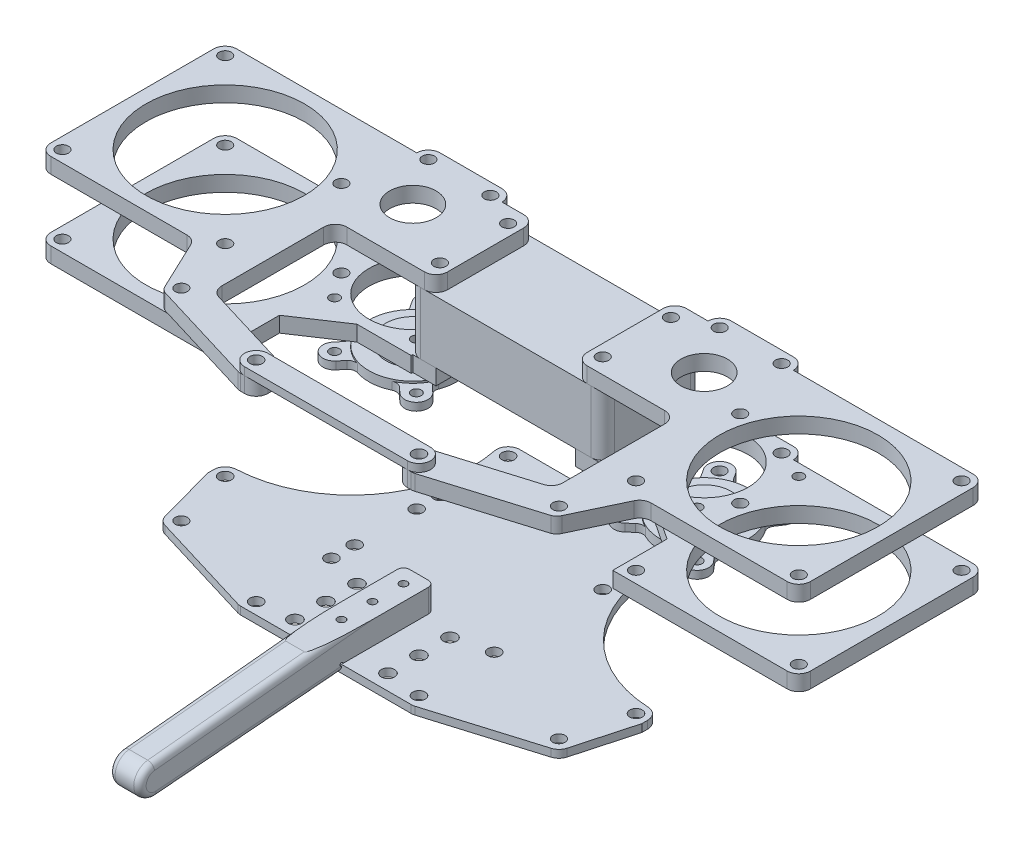
SolidWorks part; units mm, degrees
note: The reader was unsure of these and kept them because the rebuilt part matched: shared geometry of "Sketch14<2>".
material "Alum Plate"
ref_plane "Front Plane" through (0, 0, 0) normal (0, 0, 1) x (1, 0, 0)
ref_plane "Top Plane" through (0, 0, 0) normal (0, 1, 0) x (1, 0, 0)
ref_plane "Right Plane" through (0, 0, 0) normal (1, 0, 0) x (0, 0, -1)
sketch "Sketch1" plane through (0, 0, 0) normal (0, 1, 0) x (1, 0, 0)
  line L0 (0, 0) -> (117.475, 0) construction
  line L1 (-117.475, 0) -> (0, 0) construction
  line L3 (-9.525, 197.485) -> (-3.175, 197.485)
  line L4 (-9.525, 197.485) -> (-9.525, 70.485)
  line L5 (-9.525, 70.485) -> (-3.175, 70.485)
  line L6 (-3.175, 197.485) -> (-3.175, 70.485)
  line L7 (-9.525, 197.485) -> (-3.175, 70.485) construction
  line L8 (-9.525, 70.485) -> (-3.175, 197.485) construction
  line L14 (-155.575, -76.2) -> (155.575, -76.2)
  line L20 (-28.575, 38.1) -> (0, 38.1) construction
  line L21 (-6.35, 133.985) -> (0, 133.985)
  line L29 (0, 0) -> (0, -18.415) construction
  line L30 (-117.475, 0) -> (-59.6589, 19.05) construction
  line L43 (59.6589, 19.05) -> (117.475, 0) construction
  line L44 (-86.6074, 10.1707) -> (-86.2044, 10.3034)
  line L55 (-77.1578, 13.2842) -> (-76.7548, 13.417)
  line L69 (-155.575, -76.2) -> (-155.575, 38.1)
  line L70 (-155.575, 38.1) -> (155.575, 38.1)
  line L71 (155.575, -76.2) -> (155.575, 38.1)
  line L78 (0, 133.985) -> (0, -18.415)
  line L79 (0, -18.415) -> (0, -170.815) construction
  line L80 (-9.525, -234.315) -> (-3.175, -234.315) construction
  line L81 (-9.525, -234.315) -> (-9.525, -107.315) construction
  line L82 (-9.525, -107.315) -> (-3.175, -107.315) construction
  line L83 (-3.175, -234.315) -> (-3.175, -107.315) construction
  line L84 (-9.525, -234.315) -> (-3.175, -107.315) construction
  line L85 (-9.525, -107.315) -> (-3.175, -234.315) construction
  line L86 (0, -170.815) -> (-6.35, -170.815) construction
  line L87 (-38.1, -76.2) -> (-28.575, -76.2)
  line L88 (-38.1, -76.2) -> (-38.1, 38.1)
  line L89 (-38.1, 38.1) -> (-28.575, 38.1)
  line L90 (-28.575, -76.2) -> (-28.575, 38.1)
  line L91 (38.1, -76.2) -> (28.575, -76.2)
  line L92 (38.1, -76.2) -> (38.1, 38.1)
  line L93 (38.1, 38.1) -> (28.575, 38.1)
  line L94 (28.575, -76.2) -> (28.575, 38.1)
  line L95 (0, 38.1) -> (28.575, 38.1) construction
  circle A0 centre (-117.475, 0) radius 32.5
  circle A1 centre (-117.475, 0) radius 25
  circle A2 centre (117.475, 0) radius 32.5
  circle A3 centre (117.475, 0) radius 25
  circle A4 centre (-59.6589, 19.05) radius 18
  circle A5 centre (59.6589, 19.05) radius 18
  circle A8 centre (-81.6811, 11.7938) radius 4.7625
  point P8 (-6.35, 133.985)
  point P21 (117.475, 32.5)
  point P25 (59.6589, 37.05)
  point P29 (59.6589, 1.05)
  point P31 (0, -76.2)
  point P32 (-6.35, -170.815)
  point P62 (149.975, 0)
  dimension "D1" = 50
  dimension "D2" = 65
  dimension "D8" = 36
  dimension "D11" = 152.4
  dimension "D12" = 56.515
  dimension "D16" = 9.525
  dimension "D3" = 127
  dimension "D4" = 6.35
  dimension "D5" = 234.95
  dimension "D6" = 38.1
  dimension "D7" = 38.1
  dimension "D9" = 114.3
  dimension "D10" = 9.525
  dimension "D13" = 9.525
  dimension "D14" = 57.15
  dimension "D15" = 60.8736
  dimension "D18" = 19.05
sketch "Sketch2" plane through (0, 0, 0) normal (1, 0, 0) x (0, 0, -1)
  line L0 (0, 25.4) -> (0, 57.475) construction
  line L1 (-32.5, 60.975) -> (32.5, 60.975)
  line L2 (-32.5, 60.975) -> (-32.5, 53.975)
  line L3 (-32.5, 53.975) -> (32.5, 53.975)
  line L4 (32.5, 60.975) -> (32.5, 53.975)
  line L5 (-32.5, 60.975) -> (32.5, 53.975) construction
  line L6 (-32.5, 53.975) -> (32.5, 60.975) construction
  line L7 (-32.5, 92.075) -> (32.5, 92.075)
  line L8 (-32.5, 92.075) -> (-32.5, 85.075)
  line L9 (-32.5, 85.075) -> (32.5, 85.075)
  line L10 (32.5, 92.075) -> (32.5, 85.075)
  line L11 (-32.5, 92.075) -> (32.5, 85.075) construction
  line L12 (-32.5, 85.075) -> (32.5, 92.075) construction
  line L13 (-25.8191, 0) -> (33.9817, 0) construction
  line L14 (-18.415, 76.2) -> (-170.815, 76.2)
  line L15 (-76.2, 92.075) -> (38.1, 92.075)
  line L16 (-76.2, 92.075) -> (-76.2, 53.975)
  line L17 (-76.2, 53.975) -> (38.1, 53.975)
  line L18 (38.1, 92.075) -> (38.1, 53.975)
  line L19 (-5.8284, 26.8817) -> (0.4649, 73.66)
  line L20 (-18.415, 28.575) -> (-18.415, 76.2) construction
  line L21 (133.985, 0) -> (-18.415, 0) construction
  line L22 (-76.2, 85.725) -> (38.1, 85.725)
  line L23 (-76.2, 60.325) -> (38.1, 60.325)
  line L24 (-31.0016, 26.8817) -> (-37.2949, 73.66)
  line L25 (-18.415, 28.575) -> (-24.765, 64.8535) construction
  line L26 (-18.415, 76.2) -> (133.985, 76.2)
  line L32 (-76.2, 9.525) -> (38.1, 9.525)
  line L33 (-76.2, 9.525) -> (-76.2, 6.35)
  line L38 (-76.2, 6.35) -> (38.1, 6.35)
  line L39 (38.1, 9.525) -> (38.1, 6.35)
  line L40 (1.05, 41.2242) -> (37.05, 41.2242)
  line L41 (1.05, 41.2242) -> (1.05, 85.725)
  line L42 (1.05, 85.725) -> (37.05, 85.725)
  line L43 (37.05, 41.2242) -> (37.05, 85.725)
  line L44 (1.05, 41.2242) -> (37.05, 85.725) construction
  line L45 (1.05, 85.725) -> (37.05, 41.2242) construction
  line L46 (-38.1, 92.075) -> (-38.1, 53.975)
  line L47 (-38.1, 73.025) -> (0, 73.025) construction
  line L48 (0, 73.025) -> (38.1, 73.025) construction
  line L49 (-76.2, 9.525) -> (38.1, 6.35) construction
  line L50 (-76.2, 6.35) -> (38.1, 9.525) construction
  circle A0 centre (0, 25.4) radius 25.4
  circle A3 centre (-170.815, 76.2) radius 63.5
  circle A4 centre (-18.415, 76.2) radius 6.35
  circle A5 centre (-18.415, 28.575) radius 18
  circle A6 centre (133.985, 76.2) radius 63.5
  circle A7 centre (-18.415, 76.2) radius 19.05
  circle A8 centre (-18.415, 28.575) radius 12.7
  circle A9 centre (-24.765, 64.8535) radius 17.5006
  point P2 (0, 57.475)
  point P8 (0, 88.575)
  point P16 (-0.415, 28.575)
  point P28 (-36.415, 28.575)
  point P32 (19.05, 63.4746)
  point P34 (-234.315, 76.2)
  point P47 (0, 50.8)
  point P57 (-19.05, 7.9375)
  dimension "D1" = 50.8
  dimension "D8" = 38.1
  dimension "D2" = 25.4
  dimension "D11" = 12.7
  dimension "D12" = 36
  dimension "D14" = 35.0012
  dimension "D17" = 36.83
  dimension "D3" = 7
  dimension "D4" = 38.1
  dimension "D5" = 3.175
  dimension "D6" = 6.35
  dimension "D7" = 6.35
  dimension "D9" = 76.2
  dimension "D10" = 44.5008
  dimension "D13" = 47.625
  dimension "D15" = 3.175
  dimension "D16" = 25.4
  dimension "D18" = 44.45
  dimension "D19" = 6.35
sketch "Sketch5" plane through (0, 0, 0) normal (0, 1, 0) x (1, 0, 0)
  line L0 (-100.076, -18.415) -> (-28.575, -18.415) construction
  line L1 (-100.076, -4.415) -> (-68.58, -4.415)
  line L2 (-100.076, -4.415) -> (-100.076, -32.415)
  line L3 (-100.076, -32.415) -> (-68.58, -32.415)
  line L4 (-68.58, -4.415) -> (-68.58, -32.415)
  line L5 (-100.076, -4.415) -> (-68.58, -32.415) construction
  line L6 (-100.076, -32.415) -> (-68.58, -4.415) construction
  line L11 (-28.575, -76.2) -> (-28.575, 38.1) construction
  line L13 (-68.58, -0.415) -> (-28.575, -0.415)
  line L14 (-68.58, -0.415) -> (-68.58, -36.415)
  line L15 (-68.58, -36.415) -> (-28.575, -36.415)
  line L16 (-28.575, -0.415) -> (-28.575, -36.415)
  line L17 (-68.58, -0.415) -> (-28.575, -36.415) construction
  line L18 (-68.58, -36.415) -> (-28.575, -0.415) construction
  point P0 (-84.328, -18.415)
  point P10 (-48.5775, -18.415)
  dimension "D1" = 40.005
  dimension "D2" = 31.496
  dimension "D3" = 28
ref_plane "Plane1" through (0, 85.725, 0) normal (0, 1, 0) x (1, 0, 0)
ref_plane "Plane2" through (0, 60.325, 0) normal (0, -1, 0) x (-1, 0, 0)
ref_plane "Plane3" through (28.575, 0, 0) normal (1, 0, 0) x (0, 0, -1)
sketch "Sketch6" plane through (28.575, 0, 0) normal (1, 0, 0) x (0, 0, -1)
  line L0 (-18.415, 92.075) -> (-18.415, 76.2) construction
  line L2 (-76.2, 60.325) -> (-66.04, 92.075)
  line L3 (-76.2, 92.075) -> (38.1, 92.075) construction
  line L4 (-66.04, 92.075) -> (-62.865, 92.075)
  line L5 (-62.865, 92.075) -> (-62.865, 85.725)
  line L6 (-76.2, 85.725) -> (38.1, 85.725) construction
  line L7 (-62.865, 85.725) -> (-34.29, 85.725)
  line L8 (-2.54, 60.325) -> (-2.54, 53.975)
  line L10 (-32.5, 53.975) -> (32.5, 53.975) construction
  line L11 (-76.2, 53.975) -> (-76.2, 60.325)
  line L12 (-76.2, 53.975) -> (-2.54, 53.975)
  line L13 (-34.29, 85.725) -> (-34.29, 92.075)
  line L14 (-34.29, 92.075) -> (-2.54, 92.075)
  line L15 (-2.54, 85.725) -> (-2.54, 92.075)
  line L16 (-34.29, 85.725) -> (-2.54, 92.075) construction
  line L17 (-34.29, 92.075) -> (-2.54, 85.725) construction
  line L19 (-76.2, 60.325) -> (38.1, 60.325) construction
  line L20 (-2.54, 60.325) -> (38.1, 60.325)
  line L21 (-2.54, 60.325) -> (-2.54, 85.725) construction
  line L22 (-2.54, 85.725) -> (38.1, 85.725)
  line L23 (38.1, 60.325) -> (38.1, 85.725)
  line L24 (-2.54, 60.325) -> (38.1, 85.725) construction
  line L25 (-2.54, 85.725) -> (38.1, 60.325) construction
  line L26 (-2.54, 85.725) -> (-2.54, 60.325) construction
  point P10 (-18.415, 88.9)
  point P28 (17.78, 73.025)
  dimension "D2" = 44.45
  dimension "D3" = 3.175
  dimension "D4" = 31.75
extrude "Boss-Extrude1" add sketch "Sketch6" along normal up to vertex (9.525 mm away) up to point (38.1, 0, -38.1)
sketch "Sketch7" plane through (0, 85.725, 0) normal (0, 1, 0) x (1, 0, 0)
  line L0 (28.575, -62.865) -> (80.3409, -62.865)
  line L2 (155.575, -76.2) -> (155.575, 38.1) construction
  line L3 (155.575, -38.1) -> (155.575, 38.1)
  line L4 (155.575, 38.1) -> (28.575, 38.1)
  line L5 (28.575, 38.1) -> (28.575, -2.54)
  line L6 (155.575, -38.1) -> (117.475, -38.1)
  line L8 (117.475, 38.1) -> (117.475, 0) construction
  line L9 (117.475, 0) -> (117.475, -38.1) construction
  line L10 (28.575, -34.29) -> (38.1, -34.29)
  line L11 (38.1, -34.29) -> (38.1, -2.54)
  line L12 (38.1, -2.54) -> (28.575, -2.54)
  line L13 (28.575, -76.2) -> (28.575, 38.1) construction
  line L14 (28.575, -34.29) -> (28.575, -62.865)
  line L15 (117.475, -38.1) -> (92.075, -38.1)
  line L16 (92.075, -38.1) -> (80.3409, -62.865)
  circle A0 centre (117.475, 0) radius 32.5 construction
  circle A1 centre (117.475, 0) radius 32.5
  circle A3 centre (59.6589, 19.05) radius 9.525
  dimension "D1" = 51.7659
  dimension "D2" = 19.05
  dimension "D3" = 25.4
extrude "Boss-Extrude2" add sketch "Sketch7" along normal up to surface (6.35 mm away) separate body up to face at (33.3375, 92.075, 64.4525)
sketch "Sketch8" plane through (0, 60.325, 0) normal (0, -1, 0) x (-1, 0, 0)
  line L1 (-79.375, -38.1) -> (-155.575, -38.1)
  line L2 (-79.375, -38.1) -> (-79.375, 38.1) construction
  line L3 (-79.375, 38.1) -> (-155.575, 38.1)
  line L4 (-155.575, -38.1) -> (-155.575, 38.1)
  line L5 (-79.375, -38.1) -> (-155.575, 38.1) construction
  line L6 (-79.375, 38.1) -> (-155.575, -38.1) construction
  line L7 (155.575, 38.1) -> (-155.575, 38.1) construction
  line L8 (-28.575, 38.1) -> (-79.375, 38.1)
  line L12 (-79.375, -38.1) -> (-79.375, -3.175)
  line L13 (-79.375, -3.175) -> (-38.1, -3.175)
  line L14 (-38.1, -76.2) -> (-38.1, 38.1) construction
  line L15 (-38.1, -3.175) -> (-38.1, -2.54)
  line L16 (-38.1, -2.54) -> (-28.575, -2.54)
  line L17 (-28.575, -2.54) -> (-28.575, 38.1)
  circle A0 centre (-117.475, 0) radius 32.5 construction
  circle A1 centre (-117.475, 0) radius 32.5
  circle A3 centre (-59.6589, 19.05) radius 18
  circle A4 centre (-59.6589, 19.05) radius 18 construction
  dimension "D1" = 22.225
extrude "Boss-Extrude3" add sketch "Sketch8" along normal up to vertex (6.35 mm away) separate body up to point (0, 53.975, -38.1)
sketch "Sketch14" plane through (0, 60.325, 0) normal (0, 1, 0) x (1, 0, 0)
  line L0 (59.6589, 38.1) -> (59.6589, 19.05) construction
  line L1 (72.3589, 42.8625) -> (46.9589, 42.8625)
  line L2 (28.575, 38.1) -> (155.575, 38.1) construction
  line L3 (67.5964, 38.1) -> (51.7214, 38.1)
  arc A0 (67.5964, 38.1) -> (72.3589, 42.8625) centre (72.3589, 38.1) ccw
  arc A1 (46.9589, 42.8625) -> (51.7214, 38.1) centre (46.9589, 38.1) ccw
  dimension "D1" = 9.525
  dimension "D2" = 25.4
extrude "Boss-Extrude4" add sketch "Sketch14" against normal up to surface (6.35 mm away) up to face at (117.475, 53.975, -32.5)
extrude "Boss-Extrude5" add sketch "Sketch14<2>" against normal up to surface (6.35 mm away) from surface at 31.75 up to face at (67.4066, 85.725, 19.939) starting at face at (59.6589, 92.075, -28.575)
sketch "Sketch14<2>" plane through (0, 60.325, 0) normal (0, 1, 0) x (1, 0, 0) same geometry as "Sketch14"
sketch "Sketch15" plane through (0, 53.975, 0) normal (0, -1, 0) x (1, 0, 0)
  line L0 (-81.6811, -11.7938) -> (81.6811, -11.7938) construction
  line L1 (59.6589, -19.05) -> (117.475, 0) construction
  line L2 (79.375, 38.1) -> (79.375, 3.175) construction
  line L3 (155.575, 38.1) -> (79.375, 38.1) construction
  line L4 (155.575, 76.2) -> (155.575, -38.1) construction
  line L5 (-155.575, -38.1) -> (155.575, -38.1) construction
  line L6 (150.8125, 38.1) -> (155.575, 38.1)
  line L7 (155.575, 38.1) -> (155.575, 33.3375)
  line L8 (150.8125, -38.1) -> (155.575, -38.1)
  line L9 (155.575, -38.1) -> (155.575, -33.3375)
  line L10 (33.3375, -38.1) -> (33.3375, -31.75) construction
  line L11 (33.3375, -31.75) -> (33.3375, -3.81) construction
  line L12 (33.3375, -3.81) -> (33.3375, 2.54) construction
  line L13 (38.1, 2.54) -> (28.575, 2.54) construction
  line L14 (33.3375, 2.54) -> (33.3375, -3.81) construction
  line L15 (33.3375, 34.29) -> (33.3375, 40.64) construction
  line L16 (33.3375, 40.64) -> (33.3375, 56.515) construction
  line L18 (38.1, 34.29) -> (28.575, 34.29) construction
  line L19 (38.1, 2.54) -> (28.575, 2.54) construction
  line L20 (33.3375, 2.54) -> (33.3375, -3.81) construction
  line L21 (77.3274, 62.865) -> (77.3274, 58.1025) construction
  line L22 (28.575, 62.865) -> (80.3409, 62.865) construction
  line L23 (77.3274, 58.1025) -> (81.6312, 60.1417) construction
  line L24 (80.3409, 62.865) -> (92.075, 38.1) construction
  line L25 (33.3375, 56.515) -> (33.3375, 62.865) construction
  line L26 (80.3409, 62.865) -> (28.575, 62.865) construction
  circle A0 centre (46.9589, -38.1) radius 2.4892
  circle A1 centre (72.3589, -38.1) radius 2.4892
  circle A3 centre (81.6811, -11.7938) radius 2.4892
  circle A4 centre (150.8125, -33.3375) radius 2.4892
  circle A5 centre (150.8125, 33.3375) radius 2.4892
  circle A6 centre (84.1375, 33.3375) radius 2.4892
  circle A7 centre (84.1375, 33.3375) radius 4.7625 construction
  arc A8 (155.575, 33.3375) -> (150.8125, 38.1) centre (150.8125, 33.3375) ccw
  arc A9 (150.8125, -38.1) -> (155.575, -33.3375) centre (150.8125, -33.3375) ccw
  arc A10 (155.575, -33.3375) -> (150.8125, -38.1) centre (150.8125, -33.3375) ccw construction
  arc A11 (150.8125, 38.1) -> (155.575, 33.3375) centre (150.8125, 33.3375) ccw construction
  circle A12 centre (33.3375, -31.75) radius 2.4892
  circle A14 centre (33.3375, -3.81) radius 2.4892
  circle A15 centre (33.3375, 40.64) radius 2.4892
  circle A16 centre (77.3274, 58.1025) radius 2.4892
  circle A17 centre (33.3375, 56.515) radius 2.4892
  dimension "D1" = 4.9784
  dimension "D2" = 9.525
  dimension "D3" = 6.35
  dimension "D4" = 6.35
  dimension "D5" = 4.7625
extrude "Cut-Extrude9" cut sketch "Sketch15" against normal through all
sketch "Sketch16" plane through (28.575, 0, 0) normal (-1, 0, 0) x (0, 0, 1)
  circle A0 centre (18.415, 76.2) radius 6.35 construction
  circle A1 centre (18.415, 76.2) radius 6.35
extrude "Cut-Extrude10" cut sketch "Sketch16" against normal up to next (9.525 mm away)
sketch "Sketch19" plane through (0, 53.975, 0) normal (0, -1, 0) x (1, 0, 0)
  line L0 (33.3375, 76.2) -> (33.3375, 71.4375) construction
  line L1 (38.1, 76.2) -> (28.575, 76.2) construction
  line L2 (33.3375, 71.4375) -> (38.1, 71.4375) construction
  line L3 (38.1, 76.2) -> (38.1, 2.54) construction
  circle A0 centre (33.3375, -3.81) radius 2.0193
  circle A1 centre (33.3375, -31.75) radius 2.0193
  circle A2 centre (33.3375, 40.64) radius 2.0193
  circle A3 centre (33.3375, 71.4375) radius 2.0193
  circle A4 centre (33.3375, 40.64) radius 2.4892 construction
  circle A5 centre (33.3375, 56.515) radius 2.0193
  dimension "D1" = 4.0386
extrude "Cut-Extrude11" cut sketch "Sketch19" against normal through all
sketch "Sketch22" plane through (0, 53.975, 0) normal (0, -1, 0) x (1, 0, 0)
  line L0 (150.8125, -33.3375) -> (84.1375, -33.3375) construction
  line L1 (84.1375, -33.3375) -> (84.1375, 33.3375) construction
  circle A0 centre (84.1375, -33.3375) radius 2.0193
  circle A1 centre (33.3375, -31.75) radius 2.0193 construction
extrude "Cut-Extrude12" cut sketch "Sketch22" against normal up to next (6.35 mm away)
chamfer "Chamfer1" distance 12.7 distance2 19.05 1 edges at (79.375, 57.15, 3.175)
mirror "Mirror2" about plane through (0, 0, 0) normal (1, 0, 0) of bodies 139 122 141 106 108 111
sketch "Sketch17" plane through (38.1, 0, 0) normal (1, 0, 0) x (0, 0, -1)
  circle A0 centre (-18.415, 76.2) radius 6.35 construction
  circle A1 centre (-18.415, 76.2) radius 6.35
extrude "Boss-Extrude6" add sketch "Sketch17" against normal up to surface (76.2 mm away) separate body up to face at (-38.1, 76.2, 24.765)
sketch "Sketch24" plane through (0, 53.975, 0) normal (0, -1, 0) x (1, 0, 0)
  line L1 (-38.1, 76.2) -> (38.1, 76.2)
  line L2 (-38.1, 76.2) -> (-38.1, -38.1)
  line L3 (-38.1, -38.1) -> (38.1, -38.1)
  line L4 (38.1, 76.2) -> (38.1, -38.1)
  line L5 (-38.1, 76.2) -> (38.1, -38.1) construction
  line L6 (-38.1, -38.1) -> (38.1, 76.2) construction
  circle A0 centre (-33.3375, 71.4375) radius 2.5527
  circle A1 centre (33.3375, 71.4375) radius 2.5527
  circle A2 centre (33.3375, 40.64) radius 2.5527
  circle A3 centre (-33.3375, 40.64) radius 2.5527
  circle A4 centre (-33.3375, -3.81) radius 2.5527
  circle A5 centre (33.3375, -3.81) radius 2.5527
  circle A6 centre (33.3375, -31.75) radius 2.5527
  circle A7 centre (-33.3375, -31.75) radius 2.5527
  circle A8 centre (33.3375, 56.515) radius 2.5527
  circle A9 centre (-33.3375, 56.515) radius 2.5527
  point P4 (0, 19.05)
  dimension "D1" = 5.1054
extrude "Boss-Extrude8" add sketch "Sketch24" along normal blind 3.175 separate body
sketch "Sketch25" plane through (0, 53.975, 0) normal (0, 1, 0) x (1, 0, 0)
  line L1 (-19.05, -43.815) -> (6.35, -43.815)
  line L2 (-19.05, -43.815) -> (-19.05, 6.985)
  line L3 (-19.05, 6.985) -> (6.35, 6.985)
  line L4 (6.35, -43.815) -> (6.35, 6.985)
  line L5 (-19.05, -43.815) -> (6.35, 6.985) construction
  line L6 (-19.05, 6.985) -> (6.35, -43.815) construction
  line L7 (-28.575, -76.2) -> (-28.575, -2.54) construction
  point P4 (-6.35, -18.415)
  dimension "D1" = 25.4
  dimension "D2" = 50.8
  dimension "D3" = 9.525
extrude "Cut-Extrude13" cut sketch "Sketch25" against normal through all
sketch "Sketch34" plane through (0, 53.975, 0) normal (0, -1, 0) x (1, 0, 0)
  line L0 (60.325, 3.175) -> (38.1, 3.175) construction
  line L1 (-60.325, 3.175) -> (-38.1, 3.175) construction
  line L2 (-38.1, 76.2) -> (-38.1, -38.1) construction
  line L3 (38.1, -38.1) -> (38.1, 76.2) construction
  circle A0 centre (74.26, -1.5875) radius 2.0193
  circle A1 centre (74.26, -1.5875) radius 4.7625 construction
  circle A3 centre (33.3375, -3.81) radius 2.0193 construction
  circle A4 centre (59.6589, -19.05) radius 18 construction
  circle A6 centre (-74.26, -1.5875) radius 4.7625 construction
  circle A7 centre (-74.26, -1.5875) radius 2.0193
  circle A8 centre (-59.6589, -19.05) radius 18 construction
  circle A9 centre (42.8625, -3.6873) radius 2.0193
  circle A10 centre (42.8625, -3.6873) radius 4.7625 construction
  circle A11 centre (-42.8625, -3.6873) radius 2.0193
  circle A12 centre (-42.8625, -3.6873) radius 4.7625 construction
  dimension "D1" = 9.525
extrude "Cut-Extrude20" cut sketch "Sketch34" against normal up to next (6.35 mm away)
ref_plane "Plane4" through (0, 9.525, 0) normal (0, -1, 0) x (-1, 0, 0)
sketch "Sketch21" plane through (0, 9.525, 0) normal (0, -1, 0) x (-1, 0, 0)
  line L0 (-84.1375, -33.3375) -> (-84.1375, 33.3375) construction
  line L1 (-84.1375, 33.3375) -> (-33.3375, 31.75) construction
  line L2 (-33.3375, 31.75) -> (33.3375, 31.75) construction
  line L3 (33.3375, 31.75) -> (84.1375, 33.3375) construction
  line L4 (84.1375, 33.3375) -> (84.1375, -33.3375) construction
  line L5 (84.1375, -33.3375) -> (33.3375, -71.4375) construction
  line L6 (33.3375, -71.4375) -> (-33.3375, -71.4375) construction
  line L7 (-33.3375, -71.4375) -> (-84.1375, -33.3375) construction
  line L8 (-88.9, -35.7188) -> (-88.9, 38.2512)
  line L9 (-88.9, 38.2512) -> (-33.2631, 36.5125)
  line L10 (-33.2631, 36.5125) -> (33.2631, 36.5125)
  line L11 (33.2631, 36.5125) -> (88.9, 38.2512)
  line L12 (88.9, 38.2512) -> (88.9, -35.7188)
  line L14 (34.925, -76.2) -> (-34.925, -76.2)
  line L16 (-84.1375, -33.3375) -> (-77.3274, -58.1025) construction
  line L17 (-77.3274, -58.1025) -> (-33.3375, -71.4375) construction
  line L18 (33.3375, -71.4375) -> (77.3274, -58.1025) construction
  line L19 (77.3274, -58.1025) -> (84.1375, -33.3375) construction
  line L20 (-88.9, -35.7188) -> (-81.6, -62.2655)
  line L21 (88.9, -35.7188) -> (34.925, -76.2) construction
  line L22 (-34.925, -76.2) -> (-88.9, -35.7188) construction
  line L23 (-81.6, -62.2655) -> (-35.6323, -76.2)
  line L24 (35.6323, -76.2) -> (81.6, -62.2655)
  line L25 (81.6, -62.2655) -> (88.9, -35.7188)
  line L26 (-89.174, -34.7225) -> (-81.6, -62.2655) construction
  line L27 (81.6, -62.2655) -> (89.174, -34.7225) construction
  line L28 (-34.925, -76.2) -> (-35.6323, -76.2)
  line L31 (-38.1, -76.2) -> (38.1, -76.2) construction
  line L32 (-81.6, -62.2655) -> (-34.8528, -76.4363) construction
  line L33 (34.925, -76.2) -> (35.6323, -76.2)
  line L34 (34.8528, -76.4363) -> (81.6, -62.2655) construction
  circle A0 centre (-84.1375, 33.3375) radius 2.5527
  circle A1 centre (-84.1375, -33.3375) radius 2.5527
  circle A2 centre (-33.3375, 31.75) radius 2.5527
  circle A3 centre (-33.3375, 3.81) radius 2.5527
  circle A4 centre (-33.3375, -40.64) radius 2.5527
  circle A5 centre (-33.3375, -71.4375) radius 2.5527
  circle A6 centre (33.3375, -71.4375) radius 2.5527
  circle A7 centre (33.3375, -40.64) radius 2.5527
  circle A8 centre (33.3375, 3.81) radius 2.5527
  circle A9 centre (33.3375, 31.75) radius 2.5527
  circle A10 centre (84.1375, 33.3375) radius 2.5527
  circle A11 centre (84.1375, -33.3375) radius 2.5527
  circle A12 centre (-77.3274, -58.1025) radius 2.4892 construction
  circle A13 centre (77.3274, -58.1025) radius 2.4892 construction
  circle A15 centre (-77.3274, -58.1025) radius 2.4892
  circle A17 centre (-74.26, 1.5875) radius 2.5527
  circle A18 centre (74.26, 1.5875) radius 2.5527
  circle A19 centre (-42.8625, 3.6873) radius 2.5527
  circle A20 centre (42.8625, 3.6873) radius 2.5527
  circle A21 centre (77.3274, -58.1025) radius 2.4892
  dimension "D1" = 5.1054
  dimension "D2" = 4.7625
extrude "Boss-Extrude7" add sketch "Sketch21" along normal up to vertex (3.175 mm away) separate body up to point (0, 6.35, -38.1)
sketch "Sketch26" plane through (-38.1, 0, 0) normal (-1, 0, 0) x (0, 0, 1)
  line L0 (76.2, 9.525) -> (-38.1, 9.525) construction
  line L1 (-10.16, 9.525) -> (46.99, 9.525)
  line L2 (-10.16, 9.525) -> (-10.16, 50.8)
  line L3 (-10.16, 50.8) -> (46.99, 50.8)
  line L4 (46.99, 9.525) -> (46.99, 50.8)
  line L5 (-10.16, 9.525) -> (46.99, 50.8) construction
  line L6 (-10.16, 50.8) -> (46.99, 9.525) construction
  line L7 (76.2, 50.8) -> (-38.1, 50.8) construction
  line L8 (18.415, 28.575) -> (18.415, 30.1625) construction
  circle A0 centre (18.415, 28.575) radius 18 construction
  circle A1 centre (18.415, 28.575) radius 18
  point P7 (18.415, 30.1625)
  dimension "D1" = 57.15
extrude "Boss-Extrude9" add sketch "Sketch26" against normal up to surface (9.525 mm away) separate body up to face at (-28.575, 76.2, 24.765)
sketch "Sketch27" plane through (0, 9.525, 0) normal (0, -1, 0) x (1, 0, 0)
  circle A0 centre (-33.3375, -3.81) radius 2.5527 construction
  circle A1 centre (-33.3375, 40.64) radius 2.5527 construction
  circle A2 centre (-33.3375, -3.81) radius 2.5527
  circle A3 centre (-33.3375, 40.64) radius 2.5527
extrude "Cut-Extrude14" cut sketch "Sketch27" against normal through all
sketch "Sketch28" plane through (-38.1, 0, 0) normal (-1, 0, 0) x (0, 0, 1)
  line L0 (-6.3627, 6.35) -> (-1.2573, 6.35) construction
  line L1 (-10.16, 9.525) -> (0.9525, 9.525)
  line L2 (-10.16, 9.525) -> (-10.16, 14.2875)
  line L3 (-10.16, 14.2875) -> (0.9525, 14.2875)
  line L4 (0.9525, 9.525) -> (0.9525, 14.2875)
  line L5 (-10.16, 9.525) -> (0.9525, 14.2875) construction
  line L6 (-10.16, 14.2875) -> (0.9525, 9.525) construction
  line L7 (46.99, 9.525) -> (35.8775, 9.525)
  line L8 (46.99, 9.525) -> (46.99, 14.2875)
  line L9 (46.99, 14.2875) -> (35.8775, 14.2875)
  line L10 (35.8775, 9.525) -> (35.8775, 14.2875)
  line L11 (46.99, 9.525) -> (35.8775, 14.2875) construction
  line L12 (46.99, 14.2875) -> (35.8775, 9.525) construction
  line L13 (-6.3627, 6.35) -> (-1.2573, 6.35) construction
  point P4 (-4.6038, 11.9062)
  point P10 (41.4337, 11.9062)
  point P14 (-3.81, 6.35)
  dimension "D1" = 4.7625
  dimension "D2" = 4.7625
extrude "Cut-Extrude15" cut sketch "Sketch28" against normal through all
sketch "Sketch30" plane through (0, 6.35, 0) normal (0, -1, 0) x (1, 0, 0)
  line L0 (-33.3375, -3.81) -> (-33.3375, 5.715) construction
  line L1 (-33.3375, 5.715) -> (-33.3375, 31.115) construction
  line L2 (-33.3375, 31.115) -> (-33.3375, 40.64) construction
  circle A0 centre (-33.3375, 31.115) radius 2.5527
  circle A1 centre (-33.3375, 5.715) radius 2.5527
  circle A2 centre (-33.3375, -3.81) radius 2.5527 construction
  dimension "D1" = 9.525
extrude "Cut-Extrude16" cut sketch "Sketch30" against normal through all
sketch "Sketch31" plane through (0, 9.525, 0) normal (0, -1, 0) x (1, 0, 0)
  circle A0 centre (-33.3375, 5.715) radius 2.0193
  circle A1 centre (-33.3375, 31.115) radius 2.0193
  circle A2 centre (-33.3375, -3.81) radius 2.0193 construction
extrude "Cut-Extrude17" cut sketch "Sketch31" against normal up to next
sketch "Sketch32" plane through (-38.1, 0, 0) normal (-1, 0, 0) x (0, 0, 1)
  line L0 (46.99, 14.2875) -> (46.99, 50.8) construction
  line L1 (-10.16, 28.702) -> (46.99, 28.702)
  line L2 (-10.16, 28.702) -> (-10.16, 28.448)
  line L3 (-10.16, 28.448) -> (46.99, 28.448)
  line L4 (46.99, 28.702) -> (46.99, 28.448)
  line L5 (-10.16, 28.702) -> (46.99, 28.448) construction
  line L6 (-10.16, 28.448) -> (46.99, 28.702) construction
  point P0 (18.415, 28.575)
  dimension "D1" = 0.254
extrude "Cut-Extrude18" cut sketch "Sketch32" against normal through all
sketch "Sketch33" plane through (0, 6.35, 0) normal (0, -1, 0) x (1, 0, 0)
  line L0 (88.9, -38.2512) -> (88.9, 35.7188) construction
  line L1 (88.9, -25.2008) -> (88.9, 25.2008)
  line L2 (-88.9, 35.7188) -> (-88.9, -38.2512) construction
  line L3 (-88.9, -25.2008) -> (-88.9, 25.2008)
  arc A0 (88.9, -25.2008) -> (88.9, 25.2008) centre (117.475, 0) cw
  arc A1 (-88.9, 25.2008) -> (-88.9, -25.2008) centre (-117.475, 0) cw
  dimension "D1" = 38.1
extrude "Cut-Extrude19" cut sketch "Sketch33" against normal up to surface (3.175 mm away) up to face at (-33.3375, 9.525, 28.5623)
fillet "Fillet1" radius 4.7625 10 edges at (88.9, 7.9375, -38.2512) (88.9, 7.9375, 25.2008) (88.9, 7.9375, -25.2008) (-88.9, 7.9375, -25.2008) (-88.9, 7.9375, 25.2008) (-88.9, 7.9375, -38.2512) (-81.6, 7.9375, 62.2655) (-35.6323, 7.9375, 76.2) (35.6323, 7.9375, 76.2) (81.6, 7.9375, 62.2655)
ref_plane "Plane5" through (0, 41.275, 0) normal (0, -1, 0) x (-1, 0, 0)
sketch "Sketch35" plane through (0, 41.275, 0) normal (0, -1, 0) x (-1, 0, 0)
  line L0 (-59.6589, 19.05) -> (-72.3589, 38.1) construction
  line L1 (-46.9589, 38.1) -> (-59.6589, 19.05) construction
  line L2 (-59.6589, 19.05) -> (-42.8625, 3.6873) construction
  line L3 (-74.26, 1.5875) -> (-59.6589, 19.05) construction
  line L4 (-77.9137, 4.6424) -> (-74.4472, 8.7881)
  line L5 (-73.2504, 30.8514) -> (-76.3216, 35.4582)
  line L6 (-42.9963, 35.4582) -> (-46.0675, 30.8514)
  line L7 (-50.0643, 3.8203) -> (-46.0768, 0.1731)
  line L8 (-70.6064, -1.4674) -> (-67.14, 2.6783)
  line L9 (-62.8732, 15.5358) -> (-46.0768, 0.1731) construction
  line L10 (-50.9216, 40.7418) -> (-53.9928, 36.1349)
  line L11 (-62.8732, 15.5358) -> (-62.7169, 15.3928)
  line L12 (-70.6064, -1.4674) -> (-56.0053, 15.9951) construction
  line L13 (-77.9137, 4.6424) -> (-63.3125, 22.1049) construction
  line L14 (-63.6216, 16.4082) -> (-76.3216, 35.4582) construction
  line L15 (-65.3251, 36.1349) -> (-68.3963, 40.7418)
  line L16 (-50.9216, 40.7418) -> (-63.6216, 21.6918) construction
  line L18 (-43.6358, 10.8488) -> (-39.6482, 7.2016)
  line L19 (-42.9963, 35.4582) -> (-55.6963, 16.4082) construction
  circle A0 centre (-59.6589, 19.05) radius 18 construction
  arc A1 (-73.2504, 30.8514) -> (-74.4472, 8.7881) centre (-59.6589, 19.05) ccw
  arc A2 (-68.3963, 40.7418) -> (-76.3216, 35.4582) centre (-72.3589, 38.1) ccw
  arc A3 (-42.9963, 35.4582) -> (-50.9216, 40.7418) centre (-46.9589, 38.1) ccw
  arc A4 (-46.0768, 0.1731) -> (-39.6482, 7.2016) centre (-42.8625, 3.6873) ccw
  arc A5 (-77.9137, 4.6424) -> (-70.6064, -1.4674) centre (-74.26, 1.5875) ccw
  arc A6 (-53.9928, 36.1349) -> (-65.3251, 36.1349) centre (-59.6589, 19.05) ccw
  arc A7 (-43.6358, 10.8488) -> (-46.0675, 30.8514) centre (-59.6589, 19.05) ccw
  arc A8 (-67.14, 2.6783) -> (-50.0643, 3.8203) centre (-59.6589, 19.05) ccw
  circle A9 centre (-74.26, 1.5875) radius 2.0193 construction
  circle A10 centre (-42.8625, 3.6873) radius 2.0193 construction
  circle A11 centre (-46.9589, 38.1) radius 2.4892 construction
  circle A12 centre (-72.3589, 38.1) radius 2.4892 construction
  circle A13 centre (-74.26, 1.5875) radius 2.0193
  circle A14 centre (-42.8625, 3.6873) radius 2.0193
  circle A15 centre (-46.9589, 38.1) radius 2.4892
  circle A16 centre (-72.3589, 38.1) radius 2.4892
extrude "Boss-Extrude10" add sketch "Sketch35" along normal blind 3.175 separate body
sketch "Sketch36" plane through (0, 41.275, 0) normal (0, 1, 0) x (1, 0, 0)
  circle A0 centre (59.6589, 19.05) radius 18
  arc A1 (50.0643, 3.8203) -> (67.14, 2.6783) centre (59.6589, 19.05) ccw construction
extrude "Boss-Extrude11" add sketch "Sketch36" along normal offset from surface (0.762 mm away) 3.937 up to face at (72.3589, 38.1, -40.5892)
sketch "Sketch37" plane through (0, 42.037, 0) normal (0, 1, 0) x (1, 0, 0)
  circle A0 centre (59.6589, 19.05) radius 10.9982
  circle A1 centre (59.6589, 19.05) radius 18 construction
  dimension "D1" = 21.9964
extrude "Boss-Extrude12" add sketch "Sketch37" along normal offset from surface (2.413 mm away) 6.35 up to face at (72.3589, 38.1, -40.5892)
sketch "Sketch38" plane through (0, 38.1, 0) normal (0, -1, 0) x (1, 0, 0)
  circle A0 centre (59.6589, -19.05) radius 3.9878
  dimension "D1" = 7.9756
extrude "Cut-Extrude21" cut sketch "Sketch38" against normal through all
fillet "Fillet8" radius 3.175 8 edges at (46.0675, 39.6875, -30.8514) (43.6358, 39.6875, -10.8488) (53.9928, 39.6875, -36.1349) (65.3251, 39.6875, -36.1349) (73.2504, 39.6875, -30.8514) (74.4472, 39.6875, -8.7881) (50.0643, 39.6875, -3.8203) (67.14, 39.6875, -2.6783)
mirror "Mirror3" about plane through (0, 0, 0) normal (1, 0, 0) of bodies 157
sketch "Sketch39" plane through (0, 6.35, 0) normal (0, -1, 0) x (1, 0, 0)
  circle A0 centre (-59.6589, -19.05) radius 12.7
  circle A1 centre (59.6589, -19.05) radius 12.7
  circle A2 centre (-59.6589, -19.05) radius 9.525 construction
  circle A3 centre (59.6589, -19.05) radius 9.525 construction
  dimension "D1" = 25.4
extrude "Cut-Extrude22" cut sketch "Sketch39" against normal up to next (3.175 mm away)
delete or keep bodies "Body-Delete/Keep 1" type delete bodies bodies 139 109 138 143 150 149
sketch "Sketch40" plane through (0, 92.075, 0) normal (0, 1, 0) x (1, 0, 0)
  line L0 (34.9263, -76.2) -> (-34.9263, -76.2) construction
  line L1 (79.086, -63.0275) -> (36.3079, -75.9952) construction
  line L2 (-36.3079, -75.9952) -> (-79.086, -63.0275) construction
  line L3 (34.9263, -76.2) -> (28.575, -76.2)
  line L4 (79.086, -63.0275) -> (36.3079, -75.9952)
  line L5 (-36.3079, -75.9952) -> (-79.086, -63.0275)
  line L6 (-79.086, -63.0275) -> (-80.3409, -62.865)
  line L7 (-28.575, -62.865) -> (-28.575, -76.2)
  line L8 (-80.3409, -62.865) -> (-28.575, -62.865)
  line L9 (28.575, -62.865) -> (28.575, -76.2)
  line L10 (79.086, -63.0275) -> (80.3409, -62.865)
  line L11 (80.3409, -62.865) -> (28.575, -62.865)
  line L12 (-28.575, -76.2) -> (-34.9263, -76.2)
  arc A0 (34.9263, -76.2) -> (36.3079, -75.9952) centre (34.9263, -71.4375) ccw construction
  arc A1 (-36.3079, -75.9952) -> (-34.9263, -76.2) centre (-34.9263, -71.4375) ccw construction
  circle A2 centre (33.3375, -71.4375) radius 2.5527 construction
  circle A3 centre (-33.3375, -71.4375) radius 2.5527 construction
  arc A4 (34.9263, -76.2) -> (36.3079, -75.9952) centre (34.9263, -71.4375) ccw
  arc A5 (-36.3079, -75.9952) -> (-34.9263, -76.2) centre (-34.9263, -71.4375) ccw
  circle A6 centre (33.3375, -71.4375) radius 2.5527
  circle A7 centre (-33.3375, -71.4375) radius 2.5527
extrude "Boss-Extrude13" add sketch "Sketch40" against normal up to surface (6.35 mm away) up to face at (-46.9589, 85.725, -35.6108)
sketch "Sketch41" plane through (0, 92.075, 0) normal (0, 1, 0) x (1, 0, 0)
  line L0 (-69.85, -2.54) -> (69.85, -2.54)
  line L1 (69.85, -2.54) -> (69.85, -52.5566)
  line L2 (69.85, -52.5566) -> (28.575, -65.0686)
  line L3 (28.575, -76.2) -> (28.575, -34.29) construction
  line L4 (28.575, -65.0686) -> (-28.575, -65.0686)
  line L5 (-28.575, -76.2) -> (-28.575, -34.29) construction
  line L6 (-28.575, -65.0686) -> (-69.85, -52.5566)
  line L7 (-69.85, -52.5566) -> (-69.85, -2.54)
  line L8 (0, -2.54) -> (0, 0) construction
  line L9 (-79.086, -63.0275) -> (-36.3079, -75.9952) construction
  line L10 (-38.1, -2.54) -> (-28.575, -2.54) construction
  dimension "D1" = 12.7
  dimension "D2" = 69.85
extrude "Cut-Extrude23" cut sketch "Sketch41" against normal up to surface (6.35 mm away) up to face at (-46.9589, 85.725, -35.6108)
sketch "Sketch43" plane through (0, 60.325, 0) normal (0, 1, 0) x (1, 0, 0)
  line L0 (-28.575, 38.1) -> (-42.1964, 38.1) construction
  line L1 (39.6875, -2.54) -> (-39.6875, -2.54)
  line L2 (39.6875, -2.54) -> (39.6875, 38.1)
  line L3 (39.6875, 38.1) -> (-39.6875, 38.1)
  line L4 (-39.6875, -2.54) -> (-39.6875, 38.1)
  line L5 (39.6875, -2.54) -> (-39.6875, 38.1) construction
  line L6 (39.6875, 38.1) -> (-39.6875, -2.54) construction
  line L7 (-69.85, -2.54) -> (-28.575, -2.54) construction
  line L8 (0, 0) -> (0, 17.78) construction
  circle A0 centre (33.3375, 31.75) radius 2.4892 construction
  circle A1 centre (33.3375, 3.81) radius 2.4892 construction
  circle A2 centre (-33.3375, 31.75) radius 2.4892 construction
  circle A3 centre (-33.3375, 3.81) radius 2.4892 construction
  circle A4 centre (33.3375, 31.75) radius 2.4892
  circle A5 centre (33.3375, 3.81) radius 2.4892
  circle A6 centre (-33.3375, 31.75) radius 2.4892
  circle A7 centre (-33.3375, 3.81) radius 2.4892
  point P0 (0, 17.78)
  dimension "D1" = 6.35
extrude "Boss-Extrude14" add sketch "Sketch43" along normal up to surface (25.4 mm away) separate body up to face at (-46.9589, 85.725, -35.6108)
fillet "Fillet2" radius 4.7625 4 edges at (39.6875, 73.025, -38.1) (-39.6875, 73.025, -38.1) (-39.6875, 73.025, 2.54) (39.6875, 73.025, 2.54)
fillet "Fillet3" radius 4.7625 8 edges at (-92.075, 88.9, 38.1) (-80.3409, 88.9, 62.865) (-28.575, 88.9, 76.2) (-28.575, 88.9, 65.0686) (-69.85, 88.9, 52.5566) (-69.85, 88.9, 2.54) (-28.575, 88.9, -38.1) (-28.575, 88.9, 2.54)
fillet "Fillet4" radius 4.7625 8 edges at (92.075, 88.9, 38.1) (80.3409, 88.9, 62.865) (69.85, 88.9, 52.5566) (69.85, 88.9, 2.54) (28.575, 88.9, 76.2) (28.575, 88.9, 65.0686) (28.575, 88.9, -38.1) (28.575, 88.9, 2.54)
sketch "Sketch44" plane through (0, 0, 0) normal (1, 0, 0) x (0, 0, -1)
  line L0 (-76.2, 9.525) -> (-38.1, 9.525)
  line L1 (-38.1, 9.525) -> (-38.1, 19.05)
  line L2 (-38.1, 19.05) -> (-88.9, 19.05)
  line L3 (-88.9, 19.05) -> (-153.0288, 12.6688)
  line L5 (-151.8708, 0.0221) -> (-76.2, 6.35)
  line L6 (-76.2, 6.35) -> (-76.2, 9.525)
  line L7 (0, 0) -> (-18.468, 0) construction
  arc A0 (-153.0288, 12.6688) -> (-151.8708, 0.0221) centre (-152.4, 6.35) ccw
  dimension "D3" = 6.35
  dimension "D1" = 38.1
  dimension "D2" = 9.525
  dimension "D4" = 76.2
  dimension "D5" = 12.7
extrude "Boss-Extrude15" add sketch "Sketch44" along normal mid plane 12.7 separate body
sketch "Sketch45" plane through (0, 6.35, 0) normal (0, -1, 0) x (1, 0, 0)
  line L0 (6.35, 38.1) -> (-6.35, 38.1) construction
  line L1 (6.35, 38.1) -> (-6.35, 38.1) construction
  line L2 (0, 38.1) -> (0, 44.45) construction
  line L3 (0, 44.45) -> (0, 57.15) construction
  line L4 (0, 57.15) -> (0, 69.85) construction
  line L5 (0, 69.85) -> (0, 76.2) construction
  line L6 (34.9263, 76.2) -> (-34.9263, 76.2) construction
  circle A0 centre (0, 44.45) radius 2.7051
  circle A1 centre (0, 57.15) radius 2.7051
  circle A2 centre (0, 69.85) radius 2.7051
  dimension "D2" = 5.4102
  dimension "D1" = 6.35
extrude "Cut-Extrude24" cut sketch "Sketch45" against normal up to surface (3.175 mm away) up to face at (-59.6589, 9.525, -31.75)
sketch "Sketch46" plane through (0, 6.35, 0) normal (0, -1, 0) x (1, 0, 0)
  line L0 (-33.2631, -36.5125) -> (33.2631, -36.5125) construction
  line L1 (-88.9, 35.7188) -> (-88.9, 26.9408) construction
  line L2 (-84.1375, 33.3375) -> (-84.3552, 28.58) construction
  line L3 (-33.3375, -31.75) -> (-38.0054, -30.8057) construction
  arc A0 (-88.9, 28.5795) -> (-39.5184, -36.5125) centre (-86.6225, -20.9702) cw
  circle A2 centre (-42.8625, -3.6873) radius 2.5527 construction
  arc A3 (-88.9, 28.5795) -> (-39.5184, -36.5125) centre (-86.6225, -20.9702) ccw
  dimension "D1" = 4.7625
extrude "Cut-Extrude25" cut sketch "Sketch46" against normal up to surface (3.175 mm away) up to face at (0, 9.525, 41.7449)
mirror "Mirror4" about plane through (0, 0, 0) normal (1, 0, 0) of "Cut-Extrude25"
fillet "Fillet5" radius 4.7625 4 edges at (-88.9, 7.9375, 28.5795) (88.9, 7.9375, 28.5795) (39.5841, 7.9375, -36.71) (-39.5841, 7.9375, -36.71)
sketch "Sketch47" plane through (0, 92.075, 0) normal (0, 1, 0) x (1, 0, 0)
  line L0 (-33.3375, -71.4375) -> (33.3375, -71.4375) construction
  line L1 (-33.3375, -66.675) -> (33.3375, -66.675)
  line L2 (-33.3375, -76.2) -> (33.3375, -76.2)
  circle A0 centre (33.3375, -71.4375) radius 2.5527 construction
  circle A1 centre (-33.3375, -71.4375) radius 2.5527 construction
  circle A2 centre (33.3375, -71.4375) radius 2.5527
  circle A3 centre (-33.3375, -71.4375) radius 2.5527
  arc A4 (-33.3375, -66.675) -> (-33.3375, -76.2) centre (-33.3375, -71.4375) ccw
  arc A5 (33.3375, -76.2) -> (33.3375, -66.675) centre (33.3375, -71.4375) ccw
  point P6 (0, -71.4375)
extrude "Boss-Extrude16" add sketch "Sketch47" along normal blind 3.175 separate body
pattern_linear "LPattern1" count 2 spacing 19.05 along (1, 0, 0) count 2 spacing 19.05 along (-1, 0, 0) of "Cut-Extrude24"
fillet "Fillet6" radius 2.54 6 edges at (-6.35, 15.8594, 120.9644) (-6.35, 5.771, 158.7235) (6.35, 15.8594, 120.9644) (6.35, 5.771, 158.7235) (-6.35, 3.186, 114.0354) (6.35, 3.186, 114.0354)
fillet "Fillet7" radius 2.54 2 edges at (-6.35, 14.2875, 38.1) (6.35, 14.2875, 38.1)
sketch "Sketch48" plane through (0, 9.525, 0) normal (0, -1, 0) x (1, 0, 0)
  line L0 (6.35, 76.2) -> (-6.35, 76.2) construction
  line L1 (6.35, 76.2) -> (-6.35, 76.2)
sweep "Cut-Sweep1" cut path "Sketch48" circular profile diameter 1.27 parameters "D3"=1.27
sketch "Sketch58" plane through (0, 9.525, 0) normal (0, -1, 0) x (1, 0, 0)
  circle A0 centre (0, 44.45) radius 1.5875
  circle A1 centre (0, 57.15) radius 1.5875
  circle A2 centre (0, 69.85) radius 1.5875
  dimension "D1" = 3.175
extrude "Cut-Extrude26" cut sketch "Sketch58" against normal up to surface (9.525 mm away) up to face at (0, 19.05, 58.9186)
